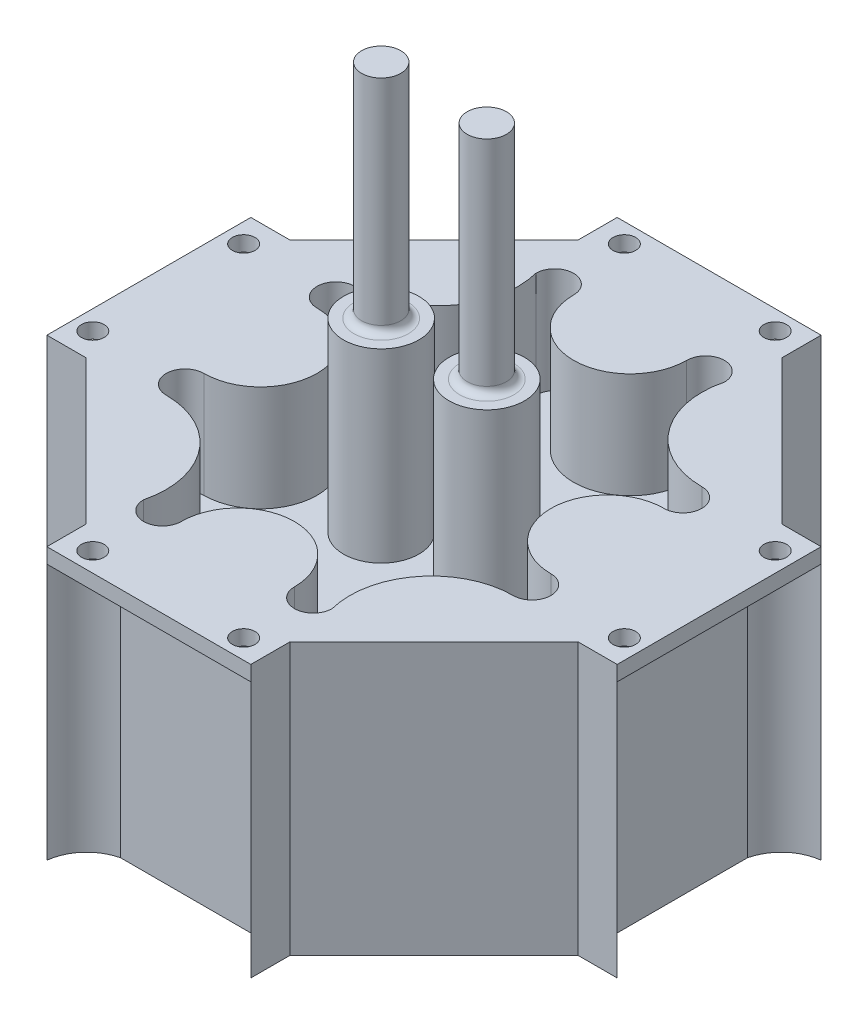
SolidWorks part; units mm, degrees
material "AISI 304"
ref_plane "Front Plane (+z tail, -z nose)" through (0, 0, 0) normal (0, 0, 1) x (1, 0, 0)
ref_plane "Top Plane (+y top of plane, -y underside)" through (0, 0, 0) normal (0, 1, 0) x (1, 0, 0)
ref_plane "Right Plane (+x right wing, -x left wing)" through (0, 0, 0) normal (1, 0, 0) x (0, 0, -1)
ref_axis "Axis2" through (0, 0, 0) along (0, 1, 0)
sketch "Sketch1" plane through (0, 0, 0) normal (0, 1, 0) x (1, 0, 0)
  line L0 (-41.4431, 0) -> (41.4431, 0) construction
  line L1 (-48.006, -48.006) -> (48.006, -48.006)
  line L2 (-48.006, -48.006) -> (-48.006, 48.006)
  line L3 (-48.006, 48.006) -> (48.006, 48.006)
  line L4 (48.006, -48.006) -> (48.006, 48.006)
  line L5 (-48.006, -48.006) -> (48.006, 48.006) construction
  line L6 (-48.006, 48.006) -> (48.006, -48.006) construction
  line L7 (41.4431, 17.1663) -> (17.1663, 41.4431)
  line L8 (17.1663, 41.4431) -> (-17.1663, 41.4431)
  line L9 (-17.1663, 41.4431) -> (-41.4431, 17.1663)
  line L10 (-41.4431, 17.1663) -> (-41.4431, -17.1663)
  line L11 (-41.4431, -17.1663) -> (-17.1663, -41.4431)
  line L12 (-17.1663, -41.4431) -> (17.1663, -41.4431)
  line L13 (17.1663, -41.4431) -> (41.4431, -17.1663)
  line L14 (41.4431, -17.1663) -> (41.4431, 17.1663)
  line L15 (-41.4431, -17.1663) -> (-48.006, -17.1663)
  line L16 (-41.4431, -17.1663) -> (-41.4431, 17.1663)
  line L17 (-41.4431, 17.1663) -> (-48.006, 17.1663)
  line L18 (-48.006, -17.1663) -> (-48.006, 17.1663)
  line L19 (0, -41.4431) -> (0, 41.4431) construction
  line L20 (-17.1663, 41.4431) -> (17.1663, 41.4431)
  line L21 (-17.1663, 41.4431) -> (-17.1663, 48.006)
  line L22 (-17.1663, 48.006) -> (17.1663, 48.006)
  line L23 (17.1663, 41.4431) -> (17.1663, 48.006)
  line L24 (41.4431, 17.1663) -> (41.4431, -17.1663)
  line L25 (41.4431, 17.1663) -> (48.006, 17.1663)
  line L26 (48.006, 17.1663) -> (48.006, -17.1663)
  line L27 (41.4431, -17.1663) -> (48.006, -17.1663)
  line L28 (17.1663, -41.4431) -> (-17.1663, -41.4431)
  line L29 (17.1663, -41.4431) -> (17.1663, -48.006)
  line L30 (17.1663, -48.006) -> (-17.1663, -48.006)
  line L31 (-17.1663, -41.4431) -> (-17.1663, -48.006)
  arc A0 (-9.525, 33.02) -> (-15.6186, 31.77) centre (-12.7, 33.02) ccw
  arc A7 (-29.21, 15.875) -> (-29.21, 9.525) centre (-29.21, 12.7) ccw
  circle A8 centre (0, 0) radius 41.4431 construction
  circle A9 centre (-8.89, 0) radius 6.35
  arc A10 (-29.21, 15.875) -> (-15.875, 33.02) centre (-29.21, 29.6333) ccw
  arc A11 (29.21, 15.875) -> (29.21, 9.525) centre (29.21, 12.7) cw
  arc A12 (9.525, 33.02) -> (15.6186, 31.77) centre (12.7, 33.02) cw
  arc A13 (29.21, 15.875) -> (15.875, 33.02) centre (29.21, 29.6333) cw
  arc A14 (-9.525, 33.02) -> (9.525, 33.02) centre (0, 33.02) ccw
  arc A15 (-29.21, -15.875) -> (-29.21, -9.525) centre (-29.21, -12.7) cw
  arc A16 (-29.21, -15.875) -> (-15.875, -33.02) centre (-29.21, -29.6333) cw
  arc A17 (29.21, -15.875) -> (29.21, -9.525) centre (29.21, -12.7) ccw
  arc A18 (29.21, -15.875) -> (15.875, -33.02) centre (29.21, -29.6333) ccw
  arc A19 (9.525, -33.02) -> (15.6186, -31.77) centre (12.7, -33.02) ccw
  arc A20 (-9.525, -33.02) -> (9.525, -33.02) centre (0, -33.02) cw
  arc A21 (-9.525, -33.02) -> (-15.6186, -31.77) centre (-12.7, -33.02) cw
  arc A22 (-29.21, 9.525) -> (-29.21, -9.525) centre (-29.21, 0) cw
  arc A23 (29.21, 9.525) -> (29.21, -9.525) centre (29.21, 0) ccw
  circle A24 centre (8.89, 0) radius 6.35
  circle A25 centre (-44.7451, 12.7) radius 1.905
  circle A26 centre (-44.7451, -12.7) radius 1.905
  arc A27 (-48.006, 17.1663) -> (-41.4431, 11.3243) centre (-48.8642, 9.5948) cw
  arc A28 (-48.006, -17.1663) -> (-41.4431, -11.3243) centre (-48.8642, -9.5948) ccw
  arc A29 (17.1663, 48.006) -> (11.3243, 41.4431) centre (9.5948, 48.8642) cw
  circle A30 centre (12.7, 44.7451) radius 1.905
  circle A31 centre (-12.7, 44.7451) radius 1.905
  arc A32 (-17.1663, 48.006) -> (-11.3243, 41.4431) centre (-9.5948, 48.8642) ccw
  arc A33 (48.006, -17.1663) -> (41.4431, -11.3243) centre (48.8642, -9.5948) cw
  circle A34 centre (44.7451, -12.7) radius 1.905
  circle A35 centre (44.7451, 12.7) radius 1.905
  arc A36 (48.006, 17.1663) -> (41.4431, 11.3243) centre (48.8642, 9.5948) ccw
  arc A37 (-17.1663, -48.006) -> (-11.3243, -41.4431) centre (-9.5948, -48.8642) cw
  circle A38 centre (-12.7, -44.7451) radius 1.905
  circle A39 centre (12.7, -44.7451) radius 1.905
  arc A40 (17.1663, -48.006) -> (11.3243, -41.4431) centre (9.5948, -48.8642) ccw
  circle A41 centre (-29.21, 12.7) radius 1.905
  circle A42 centre (-12.7, 33.02) radius 1.905
  circle A43 centre (12.7, 33.02) radius 1.905
  circle A44 centre (29.21, 12.7) radius 1.905
  circle A45 centre (29.21, -12.7) radius 1.905
  circle A46 centre (12.7, -33.02) radius 1.905
  circle A47 centre (-12.7, -33.02) radius 1.905
  circle A48 centre (-29.21, -12.7) radius 1.905
  circle A49 centre (-12.7, 33.02) radius 3.175 construction
  circle A50 centre (12.7, 33.02) radius 3.175 construction
  circle A51 centre (29.21, 12.7) radius 3.175 construction
  circle A52 centre (29.21, -12.7) radius 3.175 construction
  circle A53 centre (-12.7, -33.02) radius 3.175 construction
  circle A54 centre (12.7, -33.02) radius 3.175 construction
  circle A55 centre (-29.21, 12.7) radius 3.175 construction
  circle A56 centre (-29.21, -12.7) radius 3.175 construction
  point P0 (-12.7, 33.02)
  point P6 (-29.21, 12.7)
  point P24 (0, 0)
  point P31 (-8.89, 0)
  point P84 (0, 0)
  point P85 (0, 0)
  point P86 (0, 0)
  point P87 (0, 0)
  point P122 (0, 0)
  point P123 (43.8733, -12.7)
  point P124 (41.4431, -11.3243)
  dimension "D1" = 6.35
  dimension "D4" = 12.7
  dimension "D5" = 12.7
  dimension "D10" = 82.8862
  dimension "D12" = 3.81
  dimension "D15" = 7.62
  dimension "D2" = 96.012
  dimension "D3" = 96.012
  dimension "D6" = 29.21
  dimension "D7" = 33.02
  dimension "D8" = 12.7
  dimension "D9" = 8.89
  dimension "D13" = 3.302
  dimension "D14" = 5.842
  dimension "D17" = 1.27
  dimension "D11" = 4
  dimension "D16" = 4
extrude "Boss-Extrude1" add sketch "Sketch1" along normal blind 45.72 contours L7 L8 L9 L10 L11 L12 L13 L14
extrude "Boss-Extrude2" add sketch "Sketch1<6>" against normal blind 0.635 contours A23 A11 A13 A12 A14 A0 A10 A7 A22 A15 A16 A21 A20 A19 A18 A17 A47 A46 A45 A43 A42 A41 A9 A24 A44 A48 region at (0, 0, 0)
sketch "Sketch1<6>" plane through (0, 0, 0) normal (0, 1, 0) x (1, 0, 0) same geometry as "Sketch1"
extrude "Boss-Extrude3" add sketch "Sketch1<7>" along normal blind 43.18 contours A32 L21 L8 | L23 A29 L8 | L17 A27 L10 | A28 L15 L10 | L31 A37 L12 | A40 L29 L12 | A36 L25 L14 | L27 A33 L14 region at (-15.6442, 0, 43.0778) region at (-43.0778, 0, 15.6442) region at (15.6442, 0, 43.0778) region at (-43.0778, 0, -15.6442) region at (43.0778, 0, 15.6442) region at (-15.6442, 0, -43.0778) region at (43.0778, 0, -15.6442) region at (15.6442, 0, -43.0778)
sketch "Sketch1<7>" plane through (0, 0, 0) normal (0, 1, 0) x (1, 0, 0) same geometry as "Sketch1"
extrude "Boss-Extrude4" add sketch "Sketch1<8>" along normal blind 2.54 from offset 43.18 contours L4 A36 L24 A33 A34 A35 | L1 A40 L28 A37 A38 A39 | L2 A28 L16 A27 A25 A26 | L3 A32 L20 A29 A30 A31 | L27 A33 L14 | A36 L25 L14 | A40 L29 L12 | L31 A37 L12 | A28 L15 L10 | L17 A27 L10 | A32 L21 L8 | L23 A29 L8 region at (0, 0, 44.9194) region at (-15.6442, 0, 43.0778) region at (-43.0778, 0, 15.6442) region at (-44.9194, 0, 0) region at (15.6442, 0, 43.0778) region at (-43.0778, 0, -15.6442) region at (44.9194, 0, 0) region at (43.0778, 0, 15.6442) region at (-15.6442, 0, -43.0778) region at (0, 0, -44.9194) region at (43.0778, 0, -15.6442) region at (15.6442, 0, -43.0778)
sketch "Sketch1<8>" plane through (0, 0, 0) normal (0, 1, 0) x (1, 0, 0) same geometry as "Sketch1"
hole_wizard "CBORE for #10 Binding Head Machine Screw1" positions "Sketch2" profile "Sketch3" counterbore size "#10" standard "ANSI Inch"
sketch "Sketch2" plane through (0, 0, 0) normal (0, -1, 0) x (-1, 0, 0)
  point P0 (-8.89, 0)
  point P3 (8.89, 0)
  point P5 (0, 0)
  point P6 (6.5228, -2.5836)
  point P8 (0, 0)
  point P9 (-8.89, 0)
sketch "Sketch3" plane through (8.89, 0, 0) normal (1, 0, 0) x (0, 0, -1)
  line L0 (0, 0) -> (0, 22.9079)
  line L1 (0, 22.9079) -> (2.5527, 21.3741)
  line L2 (2.5527, 21.3741) -> (2.5527, 3.1242)
  line L3 (2.5527, 3.1242) -> (5.5562, 3.1242)
  line L5 (5.5562, 3.1242) -> (5.5563, 0.5328)
  line L6 (5.5563, 0.5328) -> (6.1913, 0)
  line L7 (6.1913, 0) -> (0, 0)
  line L8 (-5.5563, 0.5328) -> (-6.1913, 0) construction
  line L10 (0, 22.9079) -> (-2.5527, 21.3741) construction
  line L11 (0, -6.35) -> (0, 107.95) construction
  dimension "Hole Dia." = 5.1054
  dimension "Hole Depth" = 21.3741
  dimension "C'Bore Dia." = 11.1125
  dimension "C'Bore Depth" = 3.1242
  dimension "Near C'Sink Dia." = 12.3825
  dimension "Near C'Sink Angle" = 100
  dimension "Drill Angle" = 118
fillet "Fillet1" radius 1.27 16 edges at (32.385, 0, 12.7) (18.3498, 0, 21.1865) (12.7, 0, 36.195) (0, 0, 23.495) (-12.7, 0, 36.195) (-18.3498, 0, 21.1865) (-32.385, 0, 12.7) (-19.685, 0, 0) (-32.385, 0, -12.7) (-18.3498, 0, -21.1865) (-12.7, 0, -36.195) (0, 0, -23.495) (12.7, 0, -36.195) (18.3498, 0, -21.1865) (32.385, 0, -12.7) (19.685, 0, 0)
extrude "Cut-Extrude1" cut sketch "Sketch1<10>" against normal blind 17.78 from surface contours A41 | A23 A11 A13 A12 A14 A0 A10 A7 A22 A15 A16 A21 A20 A19 A18 A17 A47 A46 A45 A43 A42 A41 A9 A24 A44 A48 | A48 | A42 | A43 | A47 | A46 | A45 | A44 region at (0, 0, 0) region at (-29.21, 0, -12.7) region at (-12.7, 0, -33.02) region at (12.7, 0, -33.02) region at (29.21, 0, -12.7) region at (29.21, 0, 12.7) region at (12.7, 0, 33.02) region at (-12.7, 0, 33.02) region at (-29.21, 0, 12.7) starting at face at (0, 45.72, 0)
sketch "Sketch1<10>" plane through (0, 0, 0) normal (0, 1, 0) x (1, 0, 0) same geometry as "Sketch1"
sketch "Sketch7" plane through (0, 45.72, 0) normal (0, 1, 0) x (-1, 0, 0)
  circle A0 centre (8.89, 0) radius 6.35 construction
  circle A1 centre (-8.89, 0) radius 6.35 construction
  circle A2 centre (8.89, 0) radius 6.35
  circle A3 centre (-8.89, 0) radius 6.35
  circle A4 centre (-8.89, 0) radius 3.302
  circle A5 centre (8.89, 0) radius 3.302
  dimension "D1" = 3.048
extrude "Boss-Extrude5" add sketch "Sketch7" along normal blind 13.462 contours A4 | A3 | A5 | A2
extrude "Boss-Extrude6" add sketch "Sketch7<4>" along normal blind 50.8 contours A4 | A5 region at (8.89, 45.72, 0) region at (-8.89, 45.72, 0)
sketch "Sketch7<4>" plane through (0, 45.72, 0) normal (0, 1, 0) x (-1, 0, 0) same geometry as "Sketch7"
fillet "Fillet2" radius 1.27 2 edges at (8.89, 59.182, 3.302) (-8.89, 59.182, 3.302)
